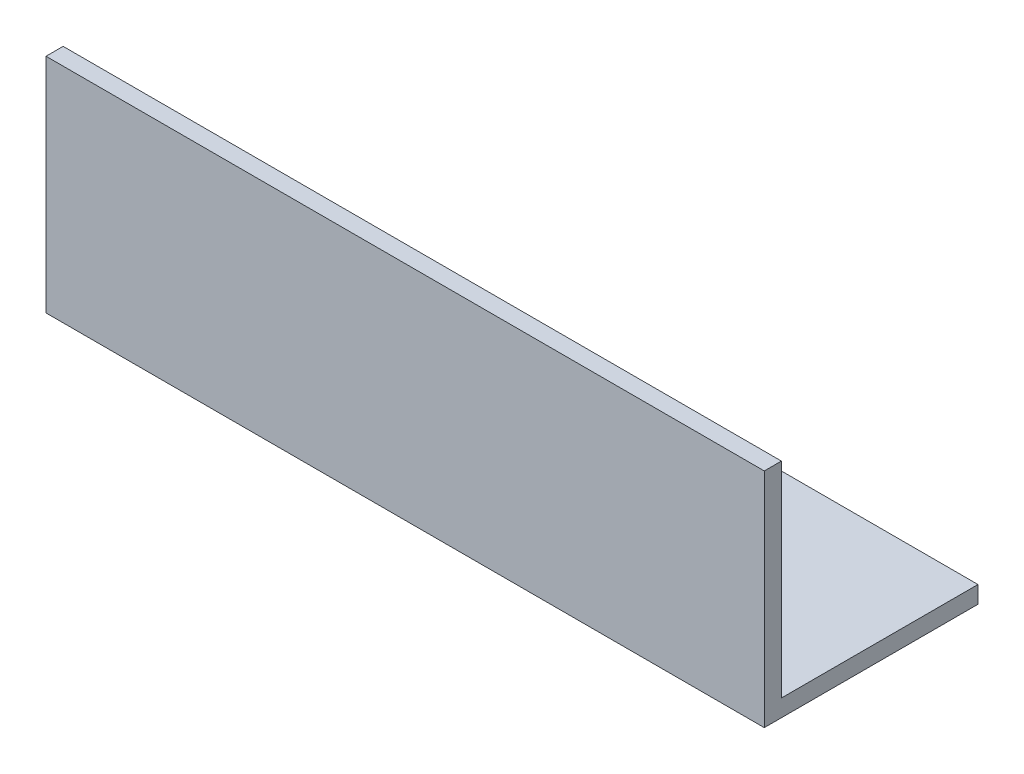
SolidWorks part; units mm, degrees
ref_plane "Front Plane" through (0, 0, 0) normal (0, 0, 1) x (1, 0, 0)
ref_plane "Top Plane" through (0, 0, 0) normal (0, 1, 0) x (1, 0, 0)
ref_plane "Right Plane" through (0, 0, 0) normal (1, 0, 0) x (0, 0, -1)
sketch "Sketch1" plane through (0, 0, 0) normal (0, 1, 0) x (1, 0, 0)
  line L0 (0, -0.79) -> (0, 19.05) construction
  line L2 (-26.99, -0.79) -> (-26.99, 19.05)
  line L3 (-26.99, 19.05) -> (26.99, 19.05)
  line L4 (26.99, -0.79) -> (26.99, 19.05)
  line L5 (-1.1193, -0.79) -> (26.99, 19.05) construction
  line L6 (-26.99, 19.05) -> (1.1193, -0.79) construction
  line L7 (-26.99, 0.8) -> (26.99, 0.8)
  line L8 (-26.99, 0.8) -> (-26.99, -0.79)
  line L9 (-26.99, -0.79) -> (26.99, -0.79)
  line L10 (26.99, 0.8) -> (26.99, -0.79)
  line L11 (-26.99, -0.79) -> (26.99, -0.79)
  line L12 (26.99, 19.05) -> (33.34, 19.05)
  line L13 (26.99, 19.05) -> (26.99, -0.79)
  line L14 (26.99, -0.79) -> (33.34, -0.79)
  line L15 (33.34, 19.05) -> (33.34, -0.79)
  line L16 (-26.99, 19.05) -> (-33.34, 19.05)
  line L17 (-26.99, 19.05) -> (-26.99, -0.79)
  line L18 (-26.99, -0.79) -> (-33.34, -0.79)
  line L19 (-33.34, 19.05) -> (-33.34, -0.79)
  line L20 (-33.34, -0.79) -> (-26.99, -0.79)
  line L21 (-33.34, -0.79) -> (-33.34, 0.8)
  line L22 (-33.34, 0.8) -> (-26.99, 0.8)
  line L23 (-26.99, -0.79) -> (-26.99, 0.8)
  line L24 (33.34, -0.79) -> (26.99, -0.79)
  line L25 (33.34, -0.79) -> (33.34, 0.8)
  line L26 (33.34, 0.8) -> (26.99, 0.8)
  line L27 (26.99, -0.79) -> (26.99, 0.8)
  circle A2 centre (-13.825, 10.08) radius 3.175
  circle A4 centre (13.825, 10.08) radius 3.175
  point P0 (0, 0)
  point P24 (26.99, -19.05)
  dimension "D9" = 6.35
  dimension "D10" = 6.35
  dimension "D1" = 53.98
  dimension "D3" = 1.59
  dimension "D11" = 27.65
  dimension "D12" = 8.97
  dimension "D13" = 13.825
  dimension "D15" = 6.35
  dimension "D16" = 6.35
extrude "Boss-Extrude1" add sketch "Sketch1" along normal blind 20.64 contours L2 L9 L4 L7 | L21 L20 L23 L22 | L25 L24 L27 L26 region at (0, 0, -0.005)
extrude "Boss-Extrude2" add sketch "Sketch1<3>" along normal blind 1.59 contours L9 L2 L4 | L2 L7 L4 L3 A4 A2 | L17 L16 L19 L18 | L13 L12 L15 L14 region at (0, 0, -0.005) region at (0, 0, -9.9143)
sketch "Sketch1<3>" plane through (0, 0, 0) normal (0, 1, 0) x (1, 0, 0) same geometry as "Sketch1"
